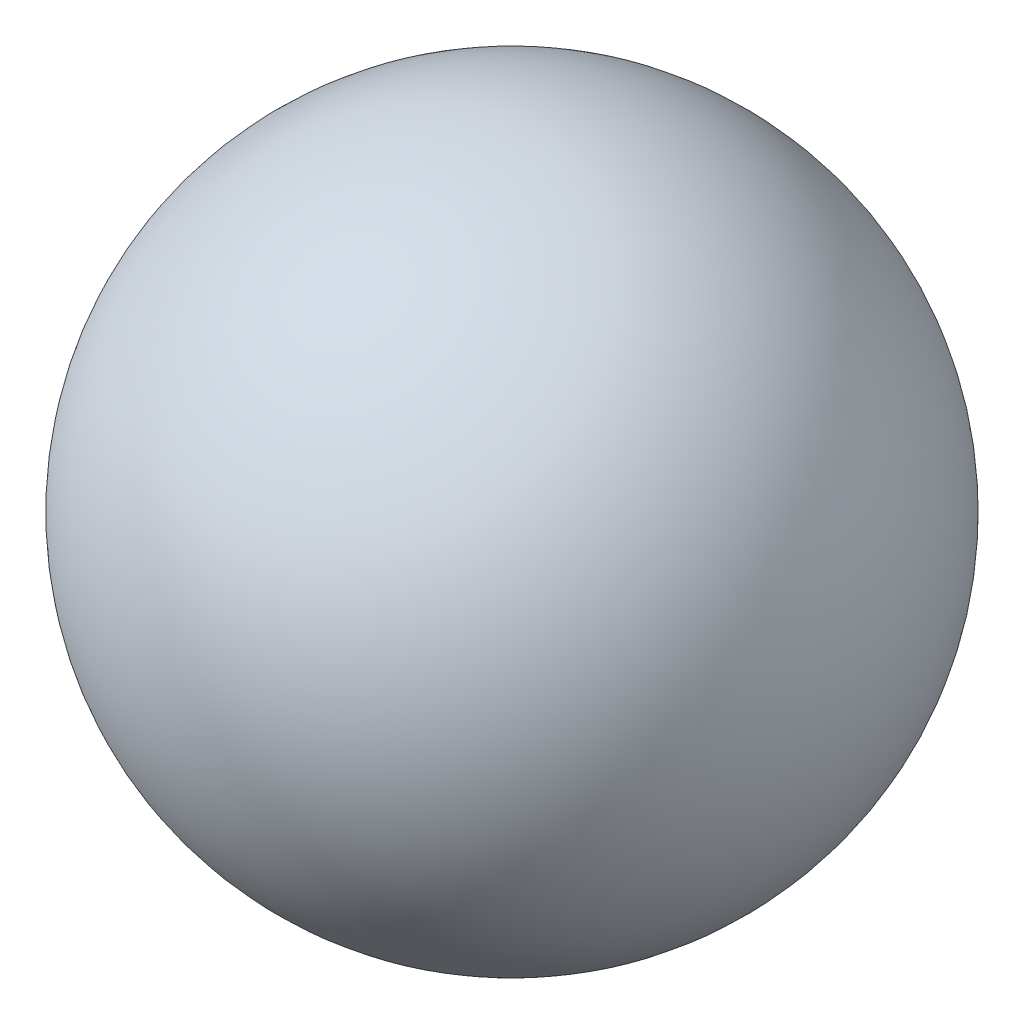
SolidWorks part; units mm, degrees
ref_plane "Front Plane" through (0, 0, 0) normal (0, 0, 1) x (1, 0, 0)
ref_plane "Top Plane" through (0, 0, 0) normal (0, 1, 0) x (1, 0, 0)
ref_plane "Right Plane" through (0, 0, 0) normal (1, 0, 0) x (0, 0, -1)
ref_axis "Axis1" through (0, -11, 0) along (0, 1, 0)
sketch "Sketch2" plane through (0, 0, 0) normal (0, 0, 1) x (1, 0, 0)
  line L0 (0, -11) -> (0, 11) construction
  line L1 (0, 100) -> (0, -100)
  arc A0 (0, 100) -> (0, -100) centre (0, 0) ccw
  dimension "D1" = 100
revolve "Revolve2" add sketch "Sketch2" angle 360 about axis through (0, -11, 0) along (0, 1, 0)
equation "\"radius\"=100"
equation "\"D1@Sketch2\"=\"radius\""
